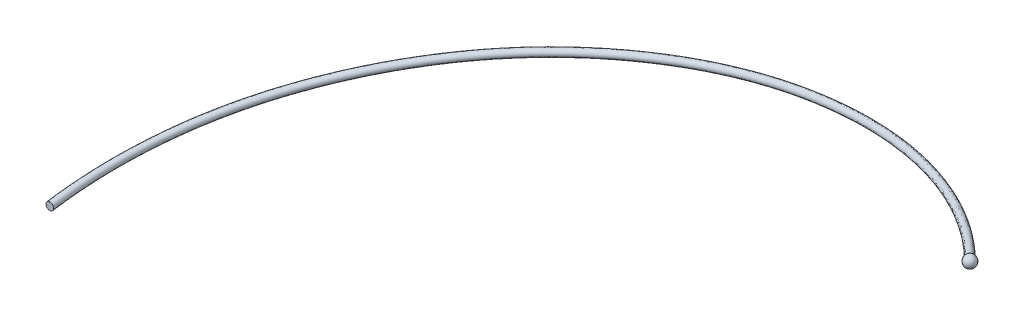
SolidWorks part; units mm, degrees
ref_plane "Front Plane" through (0, 0, 0) normal (0, 0, 1) x (1, 0, 0)
ref_plane "Top Plane" through (0, 0, 0) normal (0, 1, 0) x (1, 0, 0)
ref_plane "Right Plane" through (0, 0, 0) normal (1, 0, 0) x (0, 0, -1)
sketch "Sketch1" plane through (0, 0, 0) normal (0, 1, 0) x (1, 0, 0)
  line L2 (0, 0) -> (-3, 0)
  line L3 (0, 0.0516) -> (0, 3.0516)
  circle A0 centre (0, 0) radius 5 construction
  dimension "D1" = 10
  dimension "D2" = 3
  dimension "D3" = 3
sketch "Sketch3" plane through (0, 0, 0) normal (0, 1, 0) x (1, 0, 0)
  circle A0 centre (0, 0) radius 5 construction
  circle A1 centre (0, 0) radius 5
curve "Helix/Spiral1" pitch 5 height 1.875 radius 5 left hand yes centre (0, 0, 0) axis (0, 1, 0) start towards (0, 0, 1)
sketch "Sketch4" plane through (0, 0, 0) normal (0, 0, 1) x (1, 0, 0)
  line L0 (-1030.4251, 0) -> (50490.8277, 0) construction
  circle A0 centre (-5, 0) radius 0.05
  dimension "D1" = 5
  dimension "D2" = 0.1
sweep "Sweep1" add profiles "Sketch4" path "Helix/Spiral1"
sketch "Sketch7" plane through (0, 0, 0) normal (0, 0, 1) x (1, 0, 0)
  line L0 (0, -1000) -> (0, 49000)
ref_axis "Axis3" through (0, -1000, 0) along (0, 1, 0)
sketch "Sketch8" plane through (0, 0, 0) normal (0, 1, 0) x (1, 0, 0)
  line L0 (0, 0) -> (35355.3391, 35355.3391) construction
  line L2 (0, 0) -> (-5, 0) construction
  circle A0 centre (0, 0) radius 5 construction
  dimension "D1" = 135
ref_plane "Plane3" through (0, 0, 0) normal (0.7071, 0, 0.7071) x (0.7071, 0, -0.7071)
sketch "Sketch6" plane through (0, 0, 0) normal (0.7071, 0, 0.7071) x (0.7071, 0, -0.7071)
  line L0 (-1000, 0) -> (49000, 0) construction
  line L1 (0, -1000) -> (0, 49000) construction
  line L2 (5, 1.8) -> (5, 1.95)
  line L3 (5, -998.125) -> (5, 49001.875) construction
  line L4 (5, -998.125) -> (5, 49001.875) construction
  arc A0 (5, 1.95) -> (5, 1.8) centre (5, 1.875) ccw
  point P4 (5, 1.875)
  point P6 (5, 1.875)
  point P15 (5, 1.875)
  dimension "D3" = 0.15
  dimension "D1" = 5
  dimension "D2" = 1.875
revolve "Revolve4" add sketch "Sketch6" angle 360 about L3
sketch "Sketch9" plane through (0, 0, 0) normal (0.7071, 0, 0.7071) x (0.7071, 0, -0.7071)
  line L2 (5, 1.875) -> (5, 0) construction
  line L3 (5, 1.8) -> (5, 1.95)
  line L4 (5, 1.8463) -> (5, 1.875)
  line L6 (5, 0) -> (-5, 0) construction
  arc A2 (5, 1.95) -> (5, 1.8) centre (5, 1.875) ccw
  point P9 (5, 1.875)
  dimension "D1" = 0
sketch "Sketch13" plane through (0, 0, 0) normal (0, 0, 1) x (1, 0, 0)
  line L0 (0, 0) -> (0, 6)
  line L1 (0, -1000) -> (0, 49000) construction
  dimension "D1" = 6
sketch "Sketch10" plane through (0, 0, 0) normal (0.7071, 0, 0.7071) x (0.7071, 0, -0.7071)
  line L1 (5, 1.8463) -> (5, 1.875) construction
  line L3 (5, 1.8463) -> (5, 1.875)
  line L4 (0, 0) -> (5, 0) construction
  point P0 (5, 1.875)
sketch "Sketch15" plane through (0, 0, 0) normal (0.7071, 0, 0.7071) x (0.7071, 0, -0.7071)
  line L0 (-995, 5) -> (49005, 5) construction
  line L1 (5, -995) -> (5, 49005) construction
  point P3 (5, 5)
sketch "Sketch19" plane through (0, 0, 0) normal (0, 1, 0) x (1, 0, 0)
  line L0 (0, 0) -> (-3, 0) construction
  line L1 (-141421.3562, -141421.3562) -> (176776.6953, 176776.6953) construction
  arc A0 (-0.9798, 0.2) -> (0.5514, 0.8342) centre (0, 0) cw
  point P0 (0, 0)
  dimension "D1" = 1
  dimension "D2" = 0.2
  dimension "D3" = 0.2
sketch "Sketch20" plane through (0, 0, 0) normal (0, 1, 0) x (1, 0, 0)
  line L0 (0, -3) -> (0, 0) construction
  line L1 (0, 0) -> (3, 0) construction
  point P0 (0, 0)
  dimension "D1" = 3
  dimension "D2" = 3
sketch "Sketch12" plane through (0, 0, 0) normal (0, 0, 1) x (1, 0, 0)
  line L1 (0, 0) -> (-5, 0)
sketch "Sketch31" plane through (0, 0, 0) normal (0, 1, 0) x (1, 0, 0)
  point P0 (3.5355, 3.5355)
sketch "Sketch33" plane through (0, 0, 0) normal (0, 1, 0) x (1, 0, 0)
  line L0 (0, 0) -> (2.1213, 2.1213)
  dimension "D1" = 3
sketch "Sketch30" plane through (0, 0, 0) normal (0, 1, 0) x (1, 0, 0)
  line L0 (-3.7477, -3.7477) -> (-5.1619, -5.1619)
  line L1 (-142124.9275, -142124.9275) -> (176073.124, 176073.124) construction
  line L2 (3.7477, 3.7477) -> (5.1619, 5.1619)
  line L3 (-141421.3562, -141421.3562) -> (176776.6953, 176776.6953) construction
  arc A0 (-4.4548, -4.4548) -> (4.4548, 4.4548) centre (0, 0) cw construction
  dimension "D1" = 2
  dimension "D2" = 5.3
  dimension "D3" = 2
  dimension "D4" = 5.3
